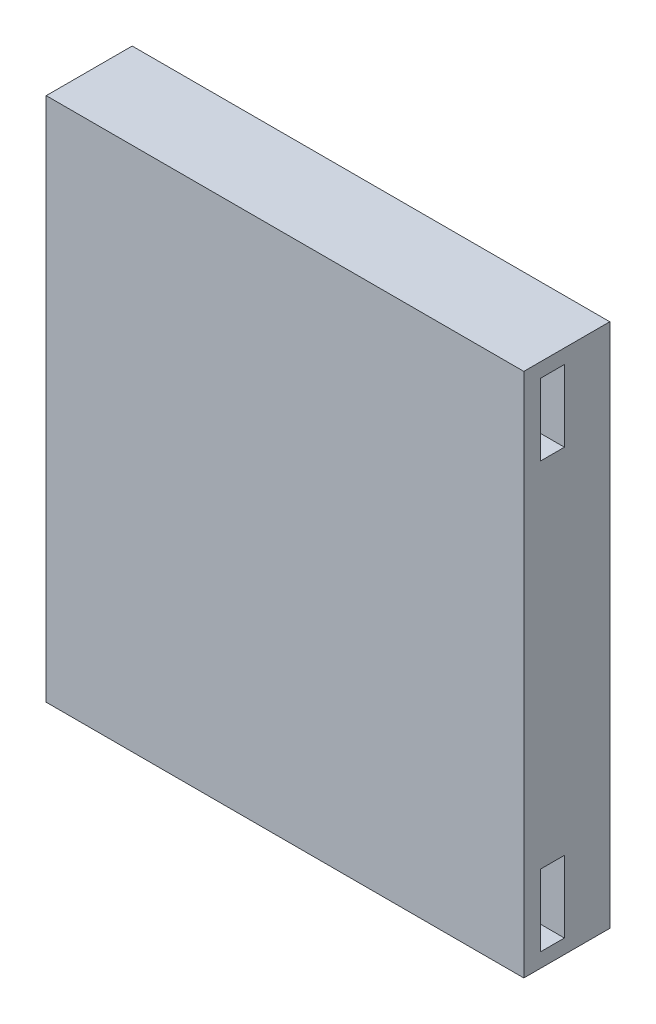
SolidWorks part; units mm, degrees
ref_plane "Front Plane" through (0, 0, 0) normal (0, 0, 1) x (1, 0, 0)
ref_plane "Top Plane" through (0, 0, 0) normal (0, 1, 0) x (1, 0, 0)
ref_plane "Right Plane" through (0, 0, 0) normal (1, 0, 0) x (0, 0, -1)
sketch "Esboço1" plane through (0, 0, 0) normal (0, 0, 1) x (1, 0, 0)
  line L0 (0, 55) -> (0, -55) construction
  line L1 (-50, 55) -> (50, 55)
  line L2 (-50, 55) -> (-50, -55)
  line L3 (-50, -55) -> (50, -55)
  line L4 (50, 55) -> (50, -55)
  point P6 (0, 0)
  dimension "D1" = 100
  dimension "D2" = 110
extrude "Ressalto-extrusão1" add sketch "Esboço1" along normal blind 18
sketch "Esboço2" plane through (0, 0, 0) normal (0, 0, -1) x (-1, 0, 0)
  line L16 (50, 0) -> (-50, 0) construction
  line L17 (50, 55) -> (50, -55) construction
  line L18 (-50, -55) -> (-50, 55) construction
  line L19 (0, 55) -> (0, -55) construction
  line L20 (-34, -16) -> (-16, -16)
  line L21 (-34, -34) -> (-34, -16)
  line L22 (-16, -34) -> (-34, -34)
  line L23 (-16, -16) -> (-16, -34)
  line L24 (16, -16) -> (16, -34)
  line L25 (34, -16) -> (16, -16)
  line L26 (16, -34) -> (34, -34)
  line L27 (34, -34) -> (34, -16)
  line L28 (-50, 55) -> (50, 55) construction
  line L29 (50, -55) -> (-50, -55) construction
  line L30 (-34, 34) -> (-34, 16)
  line L31 (-16, 34) -> (-34, 34)
  line L32 (-16, 16) -> (-16, 34)
  line L33 (-34, 16) -> (-16, 16)
  line L34 (34, 16) -> (16, 16)
  line L35 (34, 34) -> (34, 16)
  line L36 (16, 34) -> (34, 34)
  line L37 (16, 16) -> (16, 34)
extrude "Ressalto-extrusão2" add sketch "Esboço2" along normal blind 10
sketch "Esboço3" plane through (-50, 0, 0) normal (-1, 0, 0) x (0, 0, 1)
  line L28 (9.5, -52) -> (14.5, -52)
  line L29 (14.5, -52) -> (14.5, -37)
  line L30 (14.5, -37) -> (9.5, -37)
  line L31 (9.5, -37) -> (9.5, -52)
  line L32 (9.5, -52) -> (14.5, -52)
  line L33 (14.5, -52) -> (14.5, -37)
  line L34 (14.5, -37) -> (9.5, -37)
  line L35 (9.5, -37) -> (9.5, -52)
  line L36 (9.5, 37) -> (14.5, 37)
  line L37 (14.5, 37) -> (14.5, 52)
  line L38 (14.5, 52) -> (9.5, 52)
  line L39 (9.5, 52) -> (9.5, 37)
  line L40 (9.5, 37) -> (14.5, 37)
  line L41 (14.5, 37) -> (14.5, 52)
  line L42 (14.5, 52) -> (9.5, 52)
  line L43 (9.5, 52) -> (9.5, 37)
  dimension "D1" = 0
  dimension "D2" = 0
extrude "Corte-extrusão1" cut sketch "Esboço3" against normal through all
